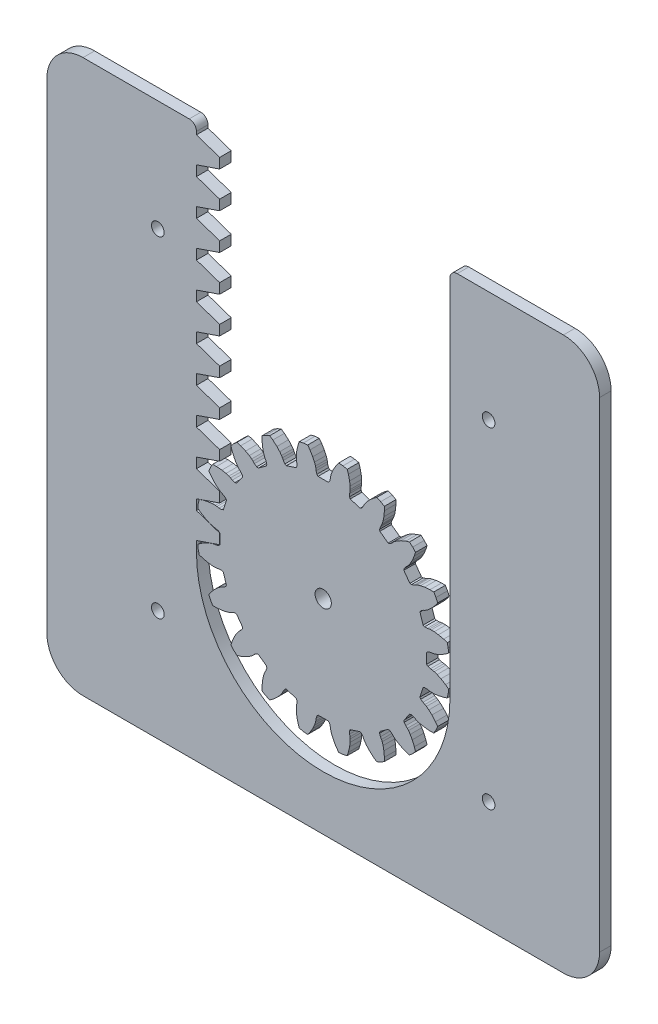
SolidWorks part; units mm, degrees
ref_plane "Front Plane" through (0, 0, 0) normal (0, 0, 1) x (1, 0, 0)
ref_plane "Top Plane" through (0, 0, 0) normal (0, 1, 0) x (1, 0, 0)
ref_plane "Right Plane" through (0, 0, 0) normal (1, 0, 0) x (0, 0, -1)
sketch "Model" plane through (0, 0, 0) normal (0, 0, 1) x (1, 0, 0)
  line L0 (-3.2331, -203.5925) -> (3.1831, -201.398)
  line L1 (3.1831, -201.398) -> (3.1831, -198.602)
  line L2 (3.1831, -198.602) -> (-3.2331, -196.4075)
  line L3 (-3.2331, -196.4075) -> (-3.2331, -193.5925)
  line L4 (-3.2331, -193.5925) -> (3.1831, -191.398)
  line L5 (3.1831, -191.398) -> (3.1831, -188.602)
  line L6 (3.1831, -188.602) -> (-3.2331, -186.4075)
  line L7 (-3.2331, -186.4075) -> (-3.2331, -183.5925)
  line L8 (-3.2331, -183.5925) -> (3.1831, -181.398)
  line L9 (3.1831, -181.398) -> (3.1831, -178.602)
  line L10 (3.1831, -178.602) -> (-3.2331, -176.4075)
  line L11 (-3.2331, -176.4075) -> (-3.2331, -173.5925)
  line L12 (-3.2331, -173.5925) -> (3.1831, -171.398)
  line L13 (3.1831, -171.398) -> (3.1831, -168.602)
  line L14 (3.1831, -168.602) -> (-3.2331, -166.4075)
  line L15 (-3.2331, -166.4075) -> (-3.2331, -163.5925)
  line L16 (-3.2331, -163.5925) -> (3.1831, -161.398)
  line L17 (3.1831, -161.398) -> (3.1831, -158.602)
  line L18 (3.1831, -158.602) -> (-3.2331, -156.4075)
  line L19 (-3.2331, -156.4075) -> (-3.2331, -153.5925)
  line L20 (-3.2331, -153.5925) -> (3.1831, -151.398)
  line L21 (3.1831, -151.398) -> (3.1831, -148.602)
  line L22 (3.1831, -148.602) -> (-3.2331, -146.4075)
  line L23 (-3.2331, -146.4075) -> (-3.2331, -143.5925)
  line L24 (-3.2331, -143.5925) -> (3.1831, -141.398)
  line L25 (3.1831, -141.398) -> (3.1831, -138.602)
  line L26 (3.1831, -138.602) -> (-3.2331, -136.4075)
  line L27 (-3.2331, -136.4075) -> (-3.2331, -133.5925)
  line L28 (-3.2331, -133.5925) -> (3.1831, -131.398)
  line L29 (3.1831, -131.398) -> (3.1831, -128.602)
  line L30 (3.1831, -128.602) -> (-3.2331, -126.4075)
  line L31 (-3.2331, -126.4075) -> (-3.2331, -123.5925)
  line L32 (-3.2331, -123.5925) -> (3.1831, -121.398)
  line L33 (3.1831, -121.398) -> (3.1831, -118.602)
  line L34 (3.1831, -118.602) -> (-3.2331, -116.4075)
  line L35 (-3.2331, -116.4075) -> (-3.2331, -113.5925)
  line L36 (-3.2331, -113.5925) -> (3.1831, -111.398)
  line L37 (3.1831, -111.398) -> (3.1831, -108.602)
  line L38 (3.1831, -108.602) -> (-3.2331, -106.4075)
  line L39 (-3.2331, -106.4075) -> (-3.2331, -103.5925)
  line L40 (-3.2331, -103.5925) -> (3.1831, -101.398)
  line L41 (3.1831, -101.398) -> (3.1831, -98.602)
  line L42 (3.1831, -98.602) -> (-3.2331, -96.4075)
  line L43 (-3.2331, -96.4075) -> (-3.2331, -93.5925)
  line L44 (-3.2331, -93.5925) -> (3.1831, -91.398)
  line L45 (3.1831, -91.398) -> (3.1831, -88.602)
  line L46 (3.1831, -88.602) -> (-3.2331, -86.4075)
  line L47 (-3.2331, -86.4075) -> (-3.2331, -83.5925)
  line L48 (-3.2331, -83.5925) -> (3.1831, -81.398)
  line L49 (3.1831, -81.398) -> (3.1831, -78.602)
  line L50 (3.1831, -78.602) -> (-3.2331, -76.4075)
  line L51 (-3.2331, -76.4075) -> (-3.2331, -73.5925)
  line L52 (-3.2331, -73.5925) -> (3.1831, -71.398)
  line L53 (3.1831, -71.398) -> (3.1831, -68.602)
  line L54 (3.1831, -68.602) -> (-3.2331, -66.4075)
  line L55 (-3.2331, -66.4075) -> (-3.2331, -63.5925)
  line L56 (-3.2331, -63.5925) -> (3.1831, -61.398)
  line L57 (3.1831, -61.398) -> (3.1831, -58.602)
  line L58 (3.1831, -58.602) -> (-3.2331, -56.4075)
  line L59 (-3.2331, -56.4075) -> (-3.2331, -53.5925)
  line L60 (-3.2331, -53.5925) -> (3.1831, -51.398)
  line L61 (3.1831, -51.398) -> (3.1831, -48.602)
  line L62 (3.1831, -48.602) -> (-3.2331, -46.4075)
  line L63 (-3.2331, -46.4075) -> (-3.2331, -43.5925)
  line L64 (-3.2331, -43.5925) -> (3.1831, -41.398)
  line L65 (3.1831, -41.398) -> (3.1831, -38.602)
  line L66 (3.1831, -38.602) -> (-3.2331, -36.4075)
  line L67 (-3.2331, -36.4075) -> (-3.2331, -33.5925)
  line L68 (-3.2331, -33.5925) -> (3.1831, -31.398)
  line L69 (3.1831, -31.398) -> (3.1831, -28.602)
  line L70 (3.1831, -28.602) -> (-3.2331, -26.4075)
  line L71 (-3.2331, -26.4075) -> (-3.2331, -23.5925)
  line L72 (-3.2331, -23.5925) -> (3.1831, -21.398)
  line L73 (3.1831, -21.398) -> (3.1831, -18.602)
  line L74 (3.1831, -18.602) -> (-3.2331, -16.4075)
  line L75 (-3.2331, -16.4075) -> (-3.2331, -13.5925)
  line L76 (-3.2331, -13.5925) -> (3.1831, -11.398)
  line L77 (3.1831, -11.398) -> (3.1831, -8.602)
  line L78 (3.1831, -8.602) -> (-3.2331, -6.4075)
  line L79 (-3.2331, -6.4075) -> (-3.2331, -3.5925)
  line L80 (-3.2331, -3.5925) -> (3.1831, -1.398)
  line L81 (3.1831, -1.398) -> (3.1831, 1.398)
  line L82 (3.1831, 1.398) -> (-3.2331, 3.5925)
  line L83 (-3.2331, 3.5925) -> (-3.2331, 6.4075)
  line L84 (-3.2331, 6.4075) -> (3.1831, 8.602)
  line L85 (3.1831, 8.602) -> (3.1831, 11.398)
  line L86 (3.1831, 11.398) -> (-3.2331, 13.5925)
  line L87 (-3.2331, 13.5925) -> (-3.2331, 16.4075)
  line L88 (-3.2331, 16.4075) -> (3.1831, 18.602)
  line L89 (3.1831, 18.602) -> (3.1831, 21.398)
  line L90 (3.1831, 21.398) -> (-3.2331, 23.5925)
  line L91 (-3.2331, 23.5925) -> (-3.2331, 26.4075)
  line L92 (-3.2331, 26.4075) -> (3.1831, 28.602)
  line L93 (3.1831, 28.602) -> (3.1831, 31.398)
  line L94 (3.1831, 31.398) -> (-3.2331, 33.5925)
  line L95 (-3.2331, 33.5925) -> (-3.2331, 36.4075)
  line L96 (-3.2331, 36.4075) -> (3.1831, 38.602)
  line L97 (3.1831, 38.602) -> (3.1831, 41.398)
  line L98 (3.1831, 41.398) -> (-3.2331, 43.5925)
  line L99 (-3.2331, 43.5925) -> (-3.2331, 46.4075)
  line L100 (-3.2331, 46.4075) -> (3.1831, 48.602)
  line L101 (3.1831, 48.602) -> (3.1831, 51.398)
  line L102 (3.1831, 51.398) -> (-3.2331, 53.5925)
  line L103 (-3.2331, 53.5925) -> (-3.2331, 56.4075)
  line L104 (-3.2331, 56.4075) -> (3.1831, 58.602)
  line L105 (3.1831, 58.602) -> (3.1831, 61.398)
  line L106 (3.1831, 61.398) -> (-3.2331, 63.5925)
  line L107 (-3.2331, 63.5925) -> (-3.2331, 66.4075)
  line L108 (-3.2331, 66.4075) -> (3.1831, 68.602)
  line L109 (3.1831, 68.602) -> (3.1831, 71.398)
  line L110 (3.1831, 71.398) -> (-3.2331, 73.5925)
  line L111 (-3.2331, 73.5925) -> (-3.2331, 76.4075)
  line L112 (-3.2331, 76.4075) -> (3.1831, 78.602)
  line L113 (3.1831, 78.602) -> (3.1831, 81.398)
  line L114 (3.1831, 81.398) -> (-3.2331, 83.5925)
  line L115 (-3.2331, 83.5925) -> (-3.2331, 86.4075)
  line L116 (-3.2331, 86.4075) -> (3.1831, 88.602)
  line L117 (3.1831, 88.602) -> (3.1831, 91.398)
  line L118 (3.1831, 91.398) -> (-3.2331, 93.5925)
  line L119 (-3.2331, 93.5925) -> (-3.2331, 96.4075)
  line L120 (-3.2331, 96.4075) -> (3.1831, 98.602)
  line L121 (3.1831, 98.602) -> (3.1831, 101.398)
  line L122 (3.1831, 101.398) -> (-3.2331, 103.5925)
  line L123 (-3.2331, 103.5925) -> (-3.2331, 106.4075)
  line L124 (-3.2331, 106.4075) -> (3.1831, 108.602)
  line L125 (3.1831, 108.602) -> (3.1831, 111.398)
  line L126 (3.1831, 111.398) -> (-3.2331, 113.5925)
  line L127 (-3.2331, 113.5925) -> (-3.2331, 116.4075)
  line L128 (-3.2331, 116.4075) -> (3.1831, 118.602)
  line L129 (3.1831, 118.602) -> (3.1831, 121.398)
  line L130 (3.1831, 121.398) -> (-3.2331, 123.5925)
  line L131 (-3.2331, 123.5925) -> (-3.2331, 126.4075)
  line L132 (-3.2331, 126.4075) -> (3.1831, 128.602)
  line L133 (3.1831, 128.602) -> (3.1831, 131.398)
  line L134 (3.1831, 131.398) -> (-3.2331, 133.5925)
  line L135 (-3.2331, 133.5925) -> (-3.2331, 136.4075)
  line L136 (-3.2331, 136.4075) -> (3.1831, 138.602)
  line L137 (3.1831, 138.602) -> (3.1831, 141.398)
  line L138 (3.1831, 141.398) -> (-3.2331, 143.5925)
  line L139 (-3.2331, 143.5925) -> (-3.2331, 146.4075)
  line L140 (-3.2331, 146.4075) -> (3.1831, 148.602)
  line L141 (3.1831, 148.602) -> (3.1831, 151.398)
  line L142 (3.1831, 151.398) -> (-3.2331, 153.5925)
  line L143 (-3.2331, 153.5925) -> (-3.2331, 156.4075)
  line L144 (-3.2331, 156.4075) -> (3.1831, 158.602)
  line L145 (3.1831, 158.602) -> (3.1831, 161.398)
  line L146 (3.1831, 161.398) -> (-3.2331, 163.5925)
  line L147 (-3.2331, 163.5925) -> (-3.2331, 166.4075)
  line L148 (-3.2331, 166.4075) -> (3.1831, 168.602)
  line L149 (3.1831, 168.602) -> (3.1831, 171.398)
  line L150 (3.1831, 171.398) -> (-3.2331, 173.5925)
  line L151 (-3.2331, 173.5925) -> (-3.2331, 176.4075)
  line L152 (-3.2331, 176.4075) -> (3.1831, 178.602)
  line L153 (3.1831, 178.602) -> (3.1831, 181.398)
  line L154 (3.1831, 181.398) -> (-3.2331, 183.5925)
  line L155 (-3.2331, 183.5925) -> (-3.2331, 186.4075)
  line L156 (-3.2331, 186.4075) -> (3.1831, 188.602)
  line L157 (3.1831, 188.602) -> (3.1831, 191.398)
  line L158 (3.1831, 191.398) -> (-3.2331, 193.5925)
  line L159 (-3.2331, 193.5925) -> (-3.2331, 196.4075)
  line L160 (-3.2331, 196.4075) -> (3.1831, 198.602)
  line L161 (3.1831, 198.602) -> (3.1831, 201.398)
  line L162 (3.1831, 201.398) -> (-3.2331, 203.5925)
  line L163 (-3.2331, 203.5925) -> (-3.2331, 205)
  line L164 (-3.2331, 205) -> (-15.9655, 205)
  line L165 (-15.9655, 205) -> (-15.9655, -205)
  line L166 (-15.9655, -205) -> (-3.2331, -205)
  line L167 (-3.2331, -205) -> (-3.2331, -203.5925)
  line L168 (-2.4761, 6.6265) -> (-2.752, 5.4774)
  line L169 (-2.752, 5.4774) -> (-2.8447, 4.2993)
  line L170 (-2.8447, 4.2993) -> (-2.0018, 3.6669)
  line L171 (-2.0018, 3.6669) -> (-0.7228, 2.9019)
  line L172 (-0.7228, 2.9019) -> (0.3292, 2.414)
  line L173 (0.3292, 2.414) -> (1.1138, 2.1457)
  line L174 (1.1138, 2.1457) -> (1.5998, 2.0345)
  line L175 (1.5998, 2.0345) -> (2.1765, 1.9649)
  line L176 (2.1765, 1.9649) -> (2.8928, 1.7388)
  line L177 (2.8928, 1.7388) -> (3.2331, 1.4208)
  line L178 (3.2331, 1.4208) -> (3.2331, -1.4208)
  line L179 (3.2331, -1.4208) -> (2.8928, -1.7388)
  line L180 (2.8928, -1.7388) -> (2.1765, -1.9649)
  line L181 (2.1765, -1.9649) -> (1.5998, -2.0345)
  line L182 (1.5998, -2.0345) -> (1.1138, -2.1457)
  line L183 (1.1138, -2.1457) -> (0.3292, -2.414)
  line L184 (0.3292, -2.414) -> (-0.7228, -2.9019)
  line L185 (-0.7228, -2.9019) -> (-2.0018, -3.6669)
  line L186 (-2.0018, -3.6669) -> (-2.8447, -4.2993)
  line L187 (-2.8447, -4.2993) -> (-2.752, -5.4774)
  line L188 (-2.752, -5.4774) -> (-2.4761, -6.6265)
  line L189 (-2.4761, -6.6265) -> (-1.4791, -6.9675)
  line L190 (-1.4791, -6.9675) -> (-0.0263, -7.2998)
  line L191 (-0.0263, -7.2998) -> (1.1251, -7.4387)
  line L192 (1.1251, -7.4387) -> (1.9541, -7.4515)
  line L193 (1.9541, -7.4515) -> (2.4507, -7.407)
  line L194 (2.4507, -7.407) -> (3.0207, -7.295)
  line L195 (3.0207, -7.295) -> (3.7718, -7.2887)
  line L196 (3.7718, -7.2887) -> (4.1937, -7.486)
  line L197 (4.1937, -7.486) -> (5.0718, -10.1885)
  line L198 (5.0718, -10.1885) -> (4.8465, -10.5961)
  line L199 (4.8465, -10.5961) -> (4.2351, -11.0325)
  line L200 (4.2351, -11.0325) -> (3.7081, -11.2769)
  line L201 (3.7081, -11.2769) -> (3.2802, -11.5328)
  line L202 (3.2802, -11.5328) -> (2.617, -12.0304)
  line L203 (2.617, -12.0304) -> (1.7672, -12.8196)
  line L204 (1.7672, -12.8196) -> (0.7872, -13.9423)
  line L205 (0.7872, -13.9423) -> (0.181, -14.8043)
  line L206 (0.181, -14.8043) -> (0.6332, -15.8961)
  line L207 (0.6332, -15.8961) -> (1.2507, -16.9037)
  line L208 (1.2507, -16.9037) -> (2.3043, -16.9199)
  line L209 (2.3043, -16.9199) -> (3.7887, -16.7869)
  line L210 (3.7887, -16.7869) -> (4.9266, -16.5633)
  line L211 (4.9266, -16.5633) -> (5.719, -16.3192)
  line L212 (5.719, -16.3192) -> (6.1775, -16.1235)
  line L213 (6.1775, -16.1235) -> (6.6851, -15.8408)
  line L214 (6.6851, -15.8408) -> (7.3975, -15.6027)
  line L215 (7.3975, -15.6027) -> (7.8597, -15.66)
  line L216 (7.8597, -15.66) -> (9.5299, -17.9589)
  line L217 (9.5299, -17.9589) -> (9.4416, -18.4162)
  line L218 (9.4416, -18.4162) -> (8.995, -19.0201)
  line L219 (8.995, -19.0201) -> (8.5693, -19.4154)
  line L220 (8.5693, -19.4154) -> (8.2414, -19.791)
  line L221 (8.2414, -19.791) -> (7.7645, -20.4692)
  line L222 (7.7645, -20.4692) -> (7.2001, -21.4824)
  line L223 (7.2001, -21.4824) -> (6.615, -22.853)
  line L224 (6.615, -22.853) -> (6.3048, -23.8601)
  line L225 (6.3048, -23.8601) -> (7.0723, -24.7587)
  line L226 (7.0723, -24.7587) -> (7.9709, -25.5262)
  line L227 (7.9709, -25.5262) -> (8.978, -25.216)
  line L228 (8.978, -25.216) -> (10.3486, -24.6309)
  line L229 (10.3486, -24.6309) -> (11.3618, -24.0665)
  line L230 (11.3618, -24.0665) -> (12.04, -23.5896)
  line L231 (12.04, -23.5896) -> (12.4155, -23.2617)
  line L232 (12.4155, -23.2617) -> (12.8109, -22.836)
  line L233 (12.8109, -22.836) -> (13.4148, -22.3894)
  line L234 (13.4148, -22.3894) -> (13.8721, -22.301)
  line L235 (13.8721, -22.301) -> (16.171, -23.9713)
  line L236 (16.171, -23.9713) -> (16.2283, -24.4335)
  line L237 (16.2283, -24.4335) -> (15.9902, -25.1459)
  line L238 (15.9902, -25.1459) -> (15.7075, -25.6535)
  line L239 (15.7075, -25.6535) -> (15.5117, -26.112)
  line L240 (15.5117, -26.112) -> (15.2677, -26.9044)
  line L241 (15.2677, -26.9044) -> (15.0441, -28.0423)
  line L242 (15.0441, -28.0423) -> (14.9111, -29.5267)
  line L243 (14.9111, -29.5267) -> (14.9273, -30.5803)
  line L244 (14.9273, -30.5803) -> (15.9349, -31.1978)
  line L245 (15.9349, -31.1978) -> (17.0267, -31.65)
  line L246 (17.0267, -31.65) -> (17.8887, -31.0438)
  line L247 (17.8887, -31.0438) -> (19.0114, -30.0638)
  line L248 (19.0114, -30.0638) -> (19.8006, -29.214)
  line L249 (19.8006, -29.214) -> (20.2982, -28.5508)
  line L250 (20.2982, -28.5508) -> (20.5541, -28.1229)
  line L251 (20.5541, -28.1229) -> (20.7985, -27.5959)
  line L252 (20.7985, -27.5959) -> (21.2349, -26.9845)
  line L253 (21.2349, -26.9845) -> (21.6425, -26.7592)
  line L254 (21.6425, -26.7592) -> (24.345, -27.6373)
  line L255 (24.345, -27.6373) -> (24.5423, -28.0592)
  line L256 (24.5423, -28.0592) -> (24.536, -28.8102)
  line L257 (24.536, -28.8102) -> (24.424, -29.3803)
  line L258 (24.424, -29.3803) -> (24.3795, -29.8769)
  line L259 (24.3795, -29.8769) -> (24.3923, -30.7059)
  line L260 (24.3923, -30.7059) -> (24.5312, -31.8573)
  line L261 (24.5312, -31.8573) -> (24.8635, -33.3101)
  line L262 (24.8635, -33.3101) -> (25.2045, -34.3071)
  line L263 (25.2045, -34.3071) -> (26.3536, -34.583)
  line L264 (26.3536, -34.583) -> (27.5317, -34.6757)
  line L265 (27.5317, -34.6757) -> (28.1641, -33.8328)
  line L266 (28.1641, -33.8328) -> (28.929, -32.5538)
  line L267 (28.929, -32.5538) -> (29.417, -31.5017)
  line L268 (29.417, -31.5017) -> (29.6853, -30.7172)
  line L269 (29.6853, -30.7172) -> (29.7965, -30.2312)
  line L270 (29.7965, -30.2312) -> (29.8661, -29.6544)
  line L271 (29.8661, -29.6544) -> (30.0922, -28.9382)
  line L272 (30.0922, -28.9382) -> (30.4102, -28.5979)
  line L273 (30.4102, -28.5979) -> (33.2518, -28.5979)
  line L274 (33.2518, -28.5979) -> (33.5698, -28.9382)
  line L275 (33.5698, -28.9382) -> (33.7959, -29.6544)
  line L276 (33.7959, -29.6544) -> (33.8655, -30.2312)
  line L277 (33.8655, -30.2312) -> (33.9767, -30.7172)
  line L278 (33.9767, -30.7172) -> (34.245, -31.5017)
  line L279 (34.245, -31.5017) -> (34.7329, -32.5538)
  line L280 (34.7329, -32.5538) -> (35.4979, -33.8328)
  line L281 (35.4979, -33.8328) -> (36.1303, -34.6757)
  line L282 (36.1303, -34.6757) -> (37.3084, -34.583)
  line L283 (37.3084, -34.583) -> (38.4575, -34.3071)
  line L284 (38.4575, -34.3071) -> (38.7985, -33.3101)
  line L285 (38.7985, -33.3101) -> (39.1308, -31.8573)
  line L286 (39.1308, -31.8573) -> (39.2697, -30.7059)
  line L287 (39.2697, -30.7059) -> (39.2825, -29.8769)
  line L288 (39.2825, -29.8769) -> (39.238, -29.3803)
  line L289 (39.238, -29.3803) -> (39.126, -28.8102)
  line L290 (39.126, -28.8102) -> (39.1197, -28.0592)
  line L291 (39.1197, -28.0592) -> (39.3169, -27.6373)
  line L292 (39.3169, -27.6373) -> (42.0195, -26.7592)
  line L293 (42.0195, -26.7592) -> (42.4271, -26.9845)
  line L294 (42.4271, -26.9845) -> (42.8635, -27.5959)
  line L295 (42.8635, -27.5959) -> (43.1079, -28.1229)
  line L296 (43.1079, -28.1229) -> (43.3638, -28.5508)
  line L297 (43.3638, -28.5508) -> (43.8614, -29.214)
  line L298 (43.8614, -29.214) -> (44.6506, -30.0638)
  line L299 (44.6506, -30.0638) -> (45.7733, -31.0438)
  line L300 (45.7733, -31.0438) -> (46.6353, -31.65)
  line L301 (46.6353, -31.65) -> (47.7271, -31.1978)
  line L302 (47.7271, -31.1978) -> (48.7347, -30.5803)
  line L303 (48.7347, -30.5803) -> (48.7509, -29.5267)
  line L304 (48.7509, -29.5267) -> (48.6179, -28.0423)
  line L305 (48.6179, -28.0423) -> (48.3943, -26.9044)
  line L306 (48.3943, -26.9044) -> (48.1502, -26.112)
  line L307 (48.1502, -26.112) -> (47.9545, -25.6535)
  line L308 (47.9545, -25.6535) -> (47.6718, -25.1459)
  line L309 (47.6718, -25.1459) -> (47.4337, -24.4335)
  line L310 (47.4337, -24.4335) -> (47.4909, -23.9713)
  line L311 (47.4909, -23.9713) -> (49.7899, -22.301)
  line L312 (49.7899, -22.301) -> (50.2472, -22.3894)
  line L313 (50.2472, -22.3894) -> (50.8511, -22.836)
  line L314 (50.8511, -22.836) -> (51.2464, -23.2617)
  line L315 (51.2464, -23.2617) -> (51.622, -23.5896)
  line L316 (51.622, -23.5896) -> (52.3002, -24.0665)
  line L317 (52.3002, -24.0665) -> (53.3134, -24.6309)
  line L318 (53.3134, -24.6309) -> (54.684, -25.216)
  line L319 (54.684, -25.216) -> (55.6911, -25.5262)
  line L320 (55.6911, -25.5262) -> (56.5897, -24.7587)
  line L321 (56.5897, -24.7587) -> (57.3572, -23.8601)
  line L322 (57.3572, -23.8601) -> (57.047, -22.853)
  line L323 (57.047, -22.853) -> (56.4619, -21.4824)
  line L324 (56.4619, -21.4824) -> (55.8975, -20.4692)
  line L325 (55.8975, -20.4692) -> (55.4206, -19.791)
  line L326 (55.4206, -19.791) -> (55.0927, -19.4154)
  line L327 (55.0927, -19.4154) -> (54.667, -19.0201)
  line L328 (54.667, -19.0201) -> (54.2204, -18.4162)
  line L329 (54.2204, -18.4162) -> (54.132, -17.9589)
  line L330 (54.132, -17.9589) -> (55.8023, -15.66)
  line L331 (55.8023, -15.66) -> (56.2645, -15.6027)
  line L332 (56.2645, -15.6027) -> (56.9769, -15.8408)
  line L333 (56.9769, -15.8408) -> (57.4844, -16.1235)
  line L334 (57.4844, -16.1235) -> (57.943, -16.3192)
  line L335 (57.943, -16.3192) -> (58.7353, -16.5633)
  line L336 (58.7353, -16.5633) -> (59.8733, -16.7869)
  line L337 (59.8733, -16.7869) -> (61.3577, -16.9199)
  line L338 (61.3577, -16.9199) -> (62.4113, -16.9037)
  line L339 (62.4113, -16.9037) -> (63.0288, -15.8961)
  line L340 (63.0288, -15.8961) -> (63.481, -14.8043)
  line L341 (63.481, -14.8043) -> (62.8748, -13.9423)
  line L342 (62.8748, -13.9423) -> (61.8948, -12.8196)
  line L343 (61.8948, -12.8196) -> (61.045, -12.0304)
  line L344 (61.045, -12.0304) -> (60.3818, -11.5328)
  line L345 (60.3818, -11.5328) -> (59.9539, -11.2769)
  line L346 (59.9539, -11.2769) -> (59.4268, -11.0325)
  line L347 (59.4268, -11.0325) -> (58.8155, -10.5961)
  line L348 (58.8155, -10.5961) -> (58.5901, -10.1885)
  line L349 (58.5901, -10.1885) -> (59.4683, -7.486)
  line L350 (59.4683, -7.486) -> (59.8901, -7.2887)
  line L351 (59.8901, -7.2887) -> (60.6412, -7.295)
  line L352 (60.6412, -7.295) -> (61.2113, -7.407)
  line L353 (61.2113, -7.407) -> (61.7079, -7.4515)
  line L354 (61.7079, -7.4515) -> (62.5369, -7.4387)
  line L355 (62.5369, -7.4387) -> (63.6883, -7.2998)
  line L356 (63.6883, -7.2998) -> (65.141, -6.9675)
  line L357 (65.141, -6.9675) -> (66.1381, -6.6265)
  line L358 (66.1381, -6.6265) -> (66.414, -5.4774)
  line L359 (66.414, -5.4774) -> (66.5067, -4.2993)
  line L360 (66.5067, -4.2993) -> (65.6638, -3.6669)
  line L361 (65.6638, -3.6669) -> (64.3848, -2.9019)
  line L362 (64.3848, -2.9019) -> (63.3327, -2.414)
  line L363 (63.3327, -2.414) -> (62.5482, -2.1457)
  line L364 (62.5482, -2.1457) -> (62.0622, -2.0345)
  line L365 (62.0622, -2.0345) -> (61.4854, -1.9649)
  line L366 (61.4854, -1.9649) -> (60.7692, -1.7388)
  line L367 (60.7692, -1.7388) -> (60.4289, -1.4208)
  line L368 (60.4289, -1.4208) -> (60.4289, 1.4208)
  line L369 (60.4289, 1.4208) -> (60.7692, 1.7388)
  line L370 (60.7692, 1.7388) -> (61.4854, 1.9649)
  line L371 (61.4854, 1.9649) -> (62.0622, 2.0345)
  line L372 (62.0622, 2.0345) -> (62.5482, 2.1457)
  line L373 (62.5482, 2.1457) -> (63.3327, 2.414)
  line L374 (63.3327, 2.414) -> (64.3848, 2.9019)
  line L375 (64.3848, 2.9019) -> (65.6638, 3.6669)
  line L376 (65.6638, 3.6669) -> (66.5067, 4.2993)
  line L377 (66.5067, 4.2993) -> (66.414, 5.4774)
  line L378 (66.414, 5.4774) -> (66.1381, 6.6265)
  line L379 (66.1381, 6.6265) -> (65.141, 6.9675)
  line L380 (65.141, 6.9675) -> (63.6883, 7.2998)
  line L381 (63.6883, 7.2998) -> (62.5369, 7.4387)
  line L382 (62.5369, 7.4387) -> (61.7079, 7.4515)
  line L383 (61.7079, 7.4515) -> (61.2113, 7.407)
  line L384 (61.2113, 7.407) -> (60.6412, 7.295)
  line L385 (60.6412, 7.295) -> (59.8901, 7.2887)
  line L386 (59.8901, 7.2887) -> (59.4683, 7.486)
  line L387 (59.4683, 7.486) -> (58.5901, 10.1885)
  line L388 (58.5901, 10.1885) -> (58.8155, 10.5961)
  line L389 (58.8155, 10.5961) -> (59.4268, 11.0325)
  line L390 (59.4268, 11.0325) -> (59.9539, 11.2769)
  line L391 (59.9539, 11.2769) -> (60.3818, 11.5328)
  line L392 (60.3818, 11.5328) -> (61.045, 12.0304)
  line L393 (61.045, 12.0304) -> (61.8948, 12.8196)
  line L394 (61.8948, 12.8196) -> (62.8748, 13.9423)
  line L395 (62.8748, 13.9423) -> (63.481, 14.8043)
  line L396 (63.481, 14.8043) -> (63.0288, 15.8961)
  line L397 (63.0288, 15.8961) -> (62.4113, 16.9037)
  line L398 (62.4113, 16.9037) -> (61.3577, 16.9199)
  line L399 (61.3577, 16.9199) -> (59.8733, 16.7869)
  line L400 (59.8733, 16.7869) -> (58.7353, 16.5633)
  line L401 (58.7353, 16.5633) -> (57.943, 16.3192)
  line L402 (57.943, 16.3192) -> (57.4844, 16.1235)
  line L403 (57.4844, 16.1235) -> (56.9769, 15.8408)
  line L404 (56.9769, 15.8408) -> (56.2645, 15.6027)
  line L405 (56.2645, 15.6027) -> (55.8023, 15.66)
  line L406 (55.8023, 15.66) -> (54.132, 17.9589)
  line L407 (54.132, 17.9589) -> (54.2204, 18.4162)
  line L408 (54.2204, 18.4162) -> (54.667, 19.0201)
  line L409 (54.667, 19.0201) -> (55.0927, 19.4154)
  line L410 (55.0927, 19.4154) -> (55.4206, 19.791)
  line L411 (55.4206, 19.791) -> (55.8975, 20.4692)
  line L412 (55.8975, 20.4692) -> (56.4619, 21.4824)
  line L413 (56.4619, 21.4824) -> (57.047, 22.853)
  line L414 (57.047, 22.853) -> (57.3572, 23.8601)
  line L415 (57.3572, 23.8601) -> (56.5897, 24.7587)
  line L416 (56.5897, 24.7587) -> (55.6911, 25.5262)
  line L417 (55.6911, 25.5262) -> (54.684, 25.216)
  line L418 (54.684, 25.216) -> (53.3134, 24.6309)
  line L419 (53.3134, 24.6309) -> (52.3002, 24.0665)
  line L420 (52.3002, 24.0665) -> (51.622, 23.5896)
  line L421 (51.622, 23.5896) -> (51.2464, 23.2617)
  line L422 (51.2464, 23.2617) -> (50.8511, 22.836)
  line L423 (50.8511, 22.836) -> (50.2472, 22.3894)
  line L424 (50.2472, 22.3894) -> (49.7899, 22.301)
  line L425 (49.7899, 22.301) -> (47.4909, 23.9713)
  line L426 (47.4909, 23.9713) -> (47.4337, 24.4335)
  line L427 (47.4337, 24.4335) -> (47.6718, 25.1459)
  line L428 (47.6718, 25.1459) -> (47.9545, 25.6535)
  line L429 (47.9545, 25.6535) -> (48.1502, 26.112)
  line L430 (48.1502, 26.112) -> (48.3943, 26.9044)
  line L431 (48.3943, 26.9044) -> (48.6179, 28.0423)
  line L432 (48.6179, 28.0423) -> (48.7509, 29.5267)
  line L433 (48.7509, 29.5267) -> (48.7347, 30.5803)
  line L434 (48.7347, 30.5803) -> (47.7271, 31.1978)
  line L435 (47.7271, 31.1978) -> (46.6353, 31.65)
  line L436 (46.6353, 31.65) -> (45.7733, 31.0438)
  line L437 (45.7733, 31.0438) -> (44.6506, 30.0638)
  line L438 (44.6506, 30.0638) -> (43.8614, 29.214)
  line L439 (43.8614, 29.214) -> (43.3638, 28.5508)
  line L440 (43.3638, 28.5508) -> (43.1079, 28.1229)
  line L441 (43.1079, 28.1229) -> (42.8635, 27.5959)
  line L442 (42.8635, 27.5959) -> (42.4271, 26.9845)
  line L443 (42.4271, 26.9845) -> (42.0195, 26.7592)
  line L444 (42.0195, 26.7592) -> (39.3169, 27.6373)
  line L445 (39.3169, 27.6373) -> (39.1197, 28.0592)
  line L446 (39.1197, 28.0592) -> (39.126, 28.8102)
  line L447 (39.126, 28.8102) -> (39.238, 29.3803)
  line L448 (39.238, 29.3803) -> (39.2825, 29.8769)
  line L449 (39.2825, 29.8769) -> (39.2697, 30.7059)
  line L450 (39.2697, 30.7059) -> (39.1308, 31.8573)
  line L451 (39.1308, 31.8573) -> (38.7985, 33.3101)
  line L452 (38.7985, 33.3101) -> (38.4575, 34.3071)
  line L453 (38.4575, 34.3071) -> (37.3084, 34.583)
  line L454 (37.3084, 34.583) -> (36.1303, 34.6757)
  line L455 (36.1303, 34.6757) -> (35.4979, 33.8328)
  line L456 (35.4979, 33.8328) -> (34.7329, 32.5538)
  line L457 (34.7329, 32.5538) -> (34.245, 31.5017)
  line L458 (34.245, 31.5017) -> (33.9767, 30.7172)
  line L459 (33.9767, 30.7172) -> (33.8655, 30.2312)
  line L460 (33.8655, 30.2312) -> (33.7959, 29.6544)
  line L461 (33.7959, 29.6544) -> (33.5698, 28.9382)
  line L462 (33.5698, 28.9382) -> (33.2518, 28.5979)
  line L463 (33.2518, 28.5979) -> (30.4102, 28.5979)
  line L464 (30.4102, 28.5979) -> (30.0922, 28.9382)
  line L465 (30.0922, 28.9382) -> (29.8661, 29.6544)
  line L466 (29.8661, 29.6544) -> (29.7965, 30.2312)
  line L467 (29.7965, 30.2312) -> (29.6853, 30.7172)
  line L468 (29.6853, 30.7172) -> (29.417, 31.5017)
  line L469 (29.417, 31.5017) -> (28.929, 32.5538)
  line L470 (28.929, 32.5538) -> (28.1641, 33.8328)
  line L471 (28.1641, 33.8328) -> (27.5317, 34.6757)
  line L472 (27.5317, 34.6757) -> (26.3536, 34.583)
  line L473 (26.3536, 34.583) -> (25.2045, 34.3071)
  line L474 (25.2045, 34.3071) -> (24.8635, 33.3101)
  line L475 (24.8635, 33.3101) -> (24.5312, 31.8573)
  line L476 (24.5312, 31.8573) -> (24.3923, 30.7059)
  line L477 (24.3923, 30.7059) -> (24.3795, 29.8769)
  line L478 (24.3795, 29.8769) -> (24.424, 29.3803)
  line L479 (24.424, 29.3803) -> (24.536, 28.8102)
  line L480 (24.536, 28.8102) -> (24.5423, 28.0592)
  line L481 (24.5423, 28.0592) -> (24.345, 27.6373)
  line L482 (24.345, 27.6373) -> (21.6425, 26.7592)
  line L483 (21.6425, 26.7592) -> (21.2349, 26.9845)
  line L484 (21.2349, 26.9845) -> (20.7985, 27.5959)
  line L485 (20.7985, 27.5959) -> (20.5541, 28.1229)
  line L486 (20.5541, 28.1229) -> (20.2982, 28.5508)
  line L487 (20.2982, 28.5508) -> (19.8006, 29.214)
  line L488 (19.8006, 29.214) -> (19.0114, 30.0638)
  line L489 (19.0114, 30.0638) -> (17.8887, 31.0438)
  line L490 (17.8887, 31.0438) -> (17.0267, 31.65)
  line L491 (17.0267, 31.65) -> (15.9349, 31.1978)
  line L492 (15.9349, 31.1978) -> (14.9273, 30.5803)
  line L493 (14.9273, 30.5803) -> (14.9111, 29.5267)
  line L494 (14.9111, 29.5267) -> (15.0441, 28.0423)
  line L495 (15.0441, 28.0423) -> (15.2677, 26.9044)
  line L496 (15.2677, 26.9044) -> (15.5117, 26.112)
  line L497 (15.5117, 26.112) -> (15.7075, 25.6535)
  line L498 (15.7075, 25.6535) -> (15.9902, 25.1459)
  line L499 (15.9902, 25.1459) -> (16.2283, 24.4335)
  line L500 (16.2283, 24.4335) -> (16.171, 23.9713)
  line L501 (16.171, 23.9713) -> (13.8721, 22.301)
  line L502 (13.8721, 22.301) -> (13.4148, 22.3894)
  line L503 (13.4148, 22.3894) -> (12.8109, 22.836)
  line L504 (12.8109, 22.836) -> (12.4155, 23.2617)
  line L505 (12.4155, 23.2617) -> (12.04, 23.5896)
  line L506 (12.04, 23.5896) -> (11.3618, 24.0665)
  line L507 (11.3618, 24.0665) -> (10.3486, 24.6309)
  line L508 (10.3486, 24.6309) -> (8.978, 25.216)
  line L509 (8.978, 25.216) -> (7.9709, 25.5262)
  line L510 (7.9709, 25.5262) -> (7.0723, 24.7587)
  line L511 (7.0723, 24.7587) -> (6.3048, 23.8601)
  line L512 (6.3048, 23.8601) -> (6.615, 22.853)
  line L513 (6.615, 22.853) -> (7.2001, 21.4824)
  line L514 (7.2001, 21.4824) -> (7.7645, 20.4692)
  line L515 (7.7645, 20.4692) -> (8.2414, 19.791)
  line L516 (8.2414, 19.791) -> (8.5693, 19.4154)
  line L517 (8.5693, 19.4154) -> (8.995, 19.0201)
  line L518 (8.995, 19.0201) -> (9.4416, 18.4162)
  line L519 (9.4416, 18.4162) -> (9.5299, 17.9589)
  line L520 (9.5299, 17.9589) -> (7.8597, 15.66)
  line L521 (7.8597, 15.66) -> (7.3975, 15.6027)
  line L522 (7.3975, 15.6027) -> (6.6851, 15.8408)
  line L523 (6.6851, 15.8408) -> (6.1775, 16.1235)
  line L524 (6.1775, 16.1235) -> (5.719, 16.3192)
  line L525 (5.719, 16.3192) -> (4.9266, 16.5633)
  line L526 (4.9266, 16.5633) -> (3.7887, 16.7869)
  line L527 (3.7887, 16.7869) -> (2.3043, 16.9199)
  line L528 (2.3043, 16.9199) -> (1.2507, 16.9037)
  line L529 (1.2507, 16.9037) -> (0.6332, 15.8961)
  line L530 (0.6332, 15.8961) -> (0.181, 14.8043)
  line L531 (0.181, 14.8043) -> (0.7872, 13.9423)
  line L532 (0.7872, 13.9423) -> (1.7672, 12.8196)
  line L533 (1.7672, 12.8196) -> (2.617, 12.0304)
  line L534 (2.617, 12.0304) -> (3.2802, 11.5328)
  line L535 (3.2802, 11.5328) -> (3.7081, 11.2769)
  line L536 (3.7081, 11.2769) -> (4.2351, 11.0325)
  line L537 (4.2351, 11.0325) -> (4.8465, 10.5961)
  line L538 (4.8465, 10.5961) -> (5.0718, 10.1885)
  line L539 (5.0718, 10.1885) -> (4.1937, 7.486)
  line L540 (4.1937, 7.486) -> (3.7718, 7.2887)
  line L541 (3.7718, 7.2887) -> (3.0207, 7.295)
  line L542 (3.0207, 7.295) -> (2.4507, 7.407)
  line L543 (2.4507, 7.407) -> (1.9541, 7.4515)
  line L544 (1.9541, 7.4515) -> (1.1251, 7.4387)
  line L545 (1.1251, 7.4387) -> (-0.0263, 7.2998)
  line L546 (-0.0263, 7.2998) -> (-1.4791, 6.9675)
  line L547 (-1.4791, 6.9675) -> (-2.4761, 6.6265)
  line L548 (31.0247, 2.1006) -> (31.479, 2.2223)
  line L549 (31.479, 2.2223) -> (31.9487, 2.2469)
  line L550 (31.9487, 2.2469) -> (32.4133, 2.1733)
  line L551 (32.4133, 2.1733) -> (32.8525, 2.0048)
  line L552 (32.8525, 2.0048) -> (33.247, 1.7486)
  line L553 (33.247, 1.7486) -> (33.5796, 1.416)
  line L554 (33.5796, 1.416) -> (33.8358, 1.0215)
  line L555 (33.8358, 1.0215) -> (34.0043, 0.5823)
  line L556 (34.0043, 0.5823) -> (34.0779, 0.1178)
  line L557 (34.0779, 0.1178) -> (34.0533, -0.352)
  line L558 (34.0533, -0.352) -> (33.9315, -0.8063)
  line L559 (33.9315, -0.8063) -> (33.718, -1.2254)
  line L560 (33.718, -1.2254) -> (33.422, -1.591)
  line L561 (33.422, -1.591) -> (33.0564, -1.887)
  line L562 (33.0564, -1.887) -> (32.6373, -2.1006)
  line L563 (32.6373, -2.1006) -> (32.183, -2.2223)
  line L564 (32.183, -2.2223) -> (31.7132, -2.2469)
  line L565 (31.7132, -2.2469) -> (31.2486, -2.1733)
  line L566 (31.2486, -2.1733) -> (30.8095, -2.0048)
  line L567 (30.8095, -2.0048) -> (30.415, -1.7486)
  line L568 (30.415, -1.7486) -> (30.0824, -1.416)
  line L569 (30.0824, -1.416) -> (29.8262, -1.0215)
  line L570 (29.8262, -1.0215) -> (29.6577, -0.5823)
  line L571 (29.6577, -0.5823) -> (29.5841, -0.1178)
  line L572 (29.5841, -0.1178) -> (29.6087, 0.352)
  line L573 (29.6087, 0.352) -> (29.7304, 0.8063)
  line L574 (29.7304, 0.8063) -> (29.944, 1.2254)
  line L575 (29.944, 1.2254) -> (30.24, 1.591)
  line L576 (30.24, 1.591) -> (30.6056, 1.887)
  line L577 (30.6056, 1.887) -> (31.0247, 2.1006)
sketch "gear_body" plane through (0, 0, 0) normal (0, 0, 1) x (1, 0, 0)
  line L0 (0, 0) -> (31.831, 0) construction
  circle A0 centre (31.831, 0) radius 2.25
  circle A1 centre (31.831, 0) radius 31.831 construction
  circle A2 centre (31.831, 0) radius 35
  dimension "D1" = 31.831
  dimension "D2" = 70
  dimension "D3" = 4.5
sketch "rack" plane through (0, 0, 0) normal (0, 0, 1) x (1, 0, 0)
  line L0 (0, 0) -> (3.1831, 0) construction
  line L1 (0, 0) -> (31.831, 0) construction
  line L2 (-3.2331, -6.4075) -> (-3.2331, 96.4075) construction
  line L3 (-3.2331, -3.5925) -> (-3.2331, -6.4075)
  line L4 (0, -6.4075) -> (0, 96.4075) construction
  line L5 (3.1831, -6.4075) -> (3.1831, 96.4075) construction
  line L6 (-3.2331, -6.4075) -> (3.1831, -6.4075) construction
  line L7 (-3.2331, -3.5925) -> (3.1831, -1.398)
  line L8 (3.1831, -1.398) -> (3.1831, 1.398)
  line L9 (3.1831, 1.398) -> (-3.2331, 3.5925)
  line L10 (-3.2331, 3.5925) -> (-3.2331, 6.4075)
  line L11 (-3.2331, 96.4075) -> (3.1831, 96.4075) construction
  line L12 (-3.2331, 13.5925) -> (-3.2331, 16.4075)
  line L13 (3.1831, 11.398) -> (-3.2331, 13.5925)
  line L14 (3.1831, 8.602) -> (3.1831, 11.398)
  line L15 (-3.2331, 6.4075) -> (3.1831, 8.602)
  line L16 (-3.2331, 23.5925) -> (-3.2331, 26.4075)
  line L17 (3.1831, 21.398) -> (-3.2331, 23.5925)
  line L18 (3.1831, 18.602) -> (3.1831, 21.398)
  line L19 (-3.2331, 16.4075) -> (3.1831, 18.602)
  line L20 (-3.2331, 33.5925) -> (-3.2331, 36.4075)
  line L21 (3.1831, 31.398) -> (-3.2331, 33.5925)
  line L22 (3.1831, 28.602) -> (3.1831, 31.398)
  line L23 (-3.2331, 26.4075) -> (3.1831, 28.602)
  line L24 (-3.2331, 43.5925) -> (-3.2331, 46.4075)
  line L25 (3.1831, 41.398) -> (-3.2331, 43.5925)
  line L26 (3.1831, 38.602) -> (3.1831, 41.398)
  line L27 (-3.2331, 36.4075) -> (3.1831, 38.602)
  line L28 (-3.2331, 53.5925) -> (-3.2331, 56.4075)
  line L29 (3.1831, 51.398) -> (-3.2331, 53.5925)
  line L30 (3.1831, 48.602) -> (3.1831, 51.398)
  line L31 (-3.2331, 46.4075) -> (3.1831, 48.602)
  line L32 (-3.2331, 63.5925) -> (-3.2331, 66.4075)
  line L33 (3.1831, 61.398) -> (-3.2331, 63.5925)
  line L34 (3.1831, 58.602) -> (3.1831, 61.398)
  line L35 (-3.2331, 56.4075) -> (3.1831, 58.602)
  line L36 (-3.2331, 73.5925) -> (-3.2331, 76.4075)
  line L37 (3.1831, 71.398) -> (-3.2331, 73.5925)
  line L38 (3.1831, 68.602) -> (3.1831, 71.398)
  line L39 (-3.2331, 66.4075) -> (3.1831, 68.602)
  line L40 (-3.2331, 83.5925) -> (-3.2331, 86.4075)
  line L41 (3.1831, 81.398) -> (-3.2331, 83.5925)
  line L42 (3.1831, 78.602) -> (3.1831, 81.398)
  line L43 (-3.2331, 76.4075) -> (3.1831, 78.602)
  line L44 (-3.2331, 93.5925) -> (-3.2331, 96.4075)
  line L45 (3.1831, 91.398) -> (-3.2331, 93.5925)
  line L46 (3.1831, 88.602) -> (3.1831, 91.398)
  line L47 (-3.2331, 86.4075) -> (3.1831, 88.602)
  line L48 (3.1831, -6.4075) -> (31.831, -6.4075) construction
  line L49 (31.831, -6.4075) -> (31.831, 96.4075) construction
  line L50 (31.831, 96.4075) -> (3.1831, 96.4075) construction
  line L51 (31.831, -6.4075) -> (66.8951, -6.4075) construction
  line L52 (31.831, 45) -> (-3.2331, 45) construction
  line L53 (66.8951, -6.4075) -> (66.8951, 96.4075)
  line L54 (31.831, -6.4075) -> (31.831, -41.4716) construction
  line L55 (31.831, 96.4075) -> (31.831, 131.4716) construction
  arc A0 (-3.2331, -6.4075) -> (66.8951, -6.4075) centre (31.831, -6.4075) ccw
  arc A1 (-3.2331, 96.4075) -> (66.8951, 96.4075) centre (31.831, 96.4075) cw
  dimension "D1" = 3.2331
  dimension "D2" = 6.4162
  dimension "D3" = 10
  dimension "D4" = 108.882
  dimension "D5" = 2.796
  dimension "D6" = 10
  dimension "D7" = 172.9432
  dimension "D8" = 70.1282
sketch "tooth_cut" plane through (0, 0, 0) normal (0, 0, 1) x (1, 0, 0)
  line L0 (0, 0) -> (31.831, 0) construction
  line L1 (3.2331, 1.4208) -> (3.2331, -1.4208)
  line L2 (31.831, 0) -> (-2.7381, 5.4752) construction
  line L3 (31.831, 0) -> (-2.7381, -5.4752) construction
  line L4 (3.2331, 1.4208) -> (2.8928, 1.7388)
  line L5 (2.8928, 1.7388) -> (2.1765, 1.9649)
  line L6 (2.1765, 1.9649) -> (1.5998, 2.0345)
  line L7 (1.5998, 2.0345) -> (1.1138, 2.1457)
  line L8 (1.1138, 2.1457) -> (0.3292, 2.414)
  line L9 (0.3292, 2.414) -> (-0.7228, 2.9019)
  line L10 (-0.7228, 2.9019) -> (-2.0018, 3.6669)
  line L11 (-2.0018, 3.6669) -> (-2.8447, 4.2993)
  line L12 (-2.8447, 4.2993) -> (-2.7381, 5.4752)
  line L13 (3.2331, -1.4208) -> (2.8928, -1.7388)
  line L14 (2.8928, -1.7388) -> (2.1765, -1.9649)
  line L15 (2.1765, -1.9649) -> (1.5998, -2.0345)
  line L16 (1.5998, -2.0345) -> (1.1138, -2.1457)
  line L17 (1.1138, -2.1457) -> (0.3292, -2.414)
  line L18 (0.3292, -2.414) -> (-0.7228, -2.9019)
  line L19 (-0.7228, -2.9019) -> (-2.0018, -3.6669)
  line L20 (-2.0018, -3.6669) -> (-2.8447, -4.2993)
  line L21 (-2.8447, -4.2993) -> (-2.7381, -5.4752)
  arc A0 (-2.7381, 5.4752) -> (-2.7381, -5.4752) centre (31.831, 0) ccw
  circle A1 centre (31.831, 0) radius 35 construction
  dimension "D3" = 18
ref_axis "Axis1" through (31.831, 0, 0) along (0, 0, 1)
sketch "Sketch5" plane through (0, 0, 0) normal (0, 0, 1) x (1, 0, 0)
  circle A0 centre (31.831, 0) radius 35
  circle A1 centre (31.831, 0) radius 35 construction
  circle A2 centre (31.831, 0) radius 2.25
  circle A3 centre (31.831, 0) radius 2.25 construction
extrude "Boss-Extrude1" add sketch "Sketch5" along normal blind 3.2
extrude "Cut-Extrude1" cut sketch "tooth_cut" along normal through all
pattern_circular "CirPattern1" count 20 over 360 about axis through (31.831, 0, 0) along (0, 0, 1) of "Cut-Extrude1"
ref_plane "Plane1" through (31.831, 0, 0) normal (1, 0, 0) x (0, 0, -1)
sketch "Sketch6" plane through (0, 0, 0) normal (0, 0, 1) x (1, 0, 0)
  line L0 (31.831, 0) -> (31.831, 96.4075) construction
  line L1 (-34.6086, -56.4716) -> (98.2705, -56.4716)
  line L2 (-44.6086, -46.4716) -> (-44.6086, 86.4075)
  line L3 (-34.6086, 96.4075) -> (-5.2331, 96.4075)
  line L4 (108.2705, -46.4716) -> (108.2705, 86.4075)
  line L5 (31.831, 96.4075) -> (31.831, 131.4716) construction
  line L6 (66.8951, -6.4075) -> (66.8951, 96.4075) construction
  line L7 (66.8951, -6.4075) -> (66.8951, 94.4075)
  line L8 (-3.2331, -6.4075) -> (-3.2331, -3.5925)
  line L9 (68.8951, 96.4075) -> (98.2705, 96.4075)
  line L10 (-24.6086, 96.4075) -> (-24.6086, -56.4716) construction
  line L11 (88.2705, -56.4716) -> (88.2705, 96.4075) construction
  line L12 (3.1831, 91.398) -> (-3.2331, 93.5925) construction
  line L13 (3.1831, 88.602) -> (3.1831, 91.398) construction
  line L14 (-3.2331, 86.4075) -> (3.1831, 88.602) construction
  line L15 (3.1831, 81.398) -> (-3.2331, 83.5925) construction
  line L16 (3.1831, 78.602) -> (3.1831, 81.398) construction
  line L17 (-3.2331, 76.4075) -> (3.1831, 78.602) construction
  line L18 (3.1831, 71.398) -> (-3.2331, 73.5925) construction
  line L19 (3.1831, 68.602) -> (3.1831, 71.398) construction
  line L20 (-3.2331, 66.4075) -> (3.1831, 68.602) construction
  line L21 (3.1831, 61.398) -> (-3.2331, 63.5925) construction
  line L22 (3.1831, 58.602) -> (3.1831, 61.398) construction
  line L23 (-3.2331, 56.4075) -> (3.1831, 58.602) construction
  line L24 (3.1831, 51.398) -> (-3.2331, 53.5925) construction
  line L25 (3.1831, 48.602) -> (3.1831, 51.398) construction
  line L26 (-3.2331, 46.4075) -> (3.1831, 48.602) construction
  line L27 (3.1831, 41.398) -> (-3.2331, 43.5925) construction
  line L28 (3.1831, 38.602) -> (3.1831, 41.398) construction
  line L29 (-3.2331, 36.4075) -> (3.1831, 38.602) construction
  line L30 (3.1831, 31.398) -> (-3.2331, 33.5925) construction
  line L31 (3.1831, 28.602) -> (3.1831, 31.398) construction
  line L32 (-3.2331, 26.4075) -> (3.1831, 28.602) construction
  line L33 (3.1831, 21.398) -> (-3.2331, 23.5925) construction
  line L34 (-3.2331, 16.4075) -> (3.1831, 18.602) construction
  line L35 (3.1831, 11.398) -> (-3.2331, 13.5925) construction
  line L36 (-3.2331, 6.4075) -> (3.1831, 8.602) construction
  line L37 (3.1831, 8.602) -> (3.1831, 11.398) construction
  line L38 (3.1831, 18.602) -> (3.1831, 21.398) construction
  line L39 (3.1831, 1.398) -> (-3.2331, 3.5925) construction
  line L40 (-3.2331, -3.5925) -> (3.1831, -1.398) construction
  line L41 (3.1831, -1.398) -> (3.1831, 1.398) construction
  line L42 (3.1831, 91.398) -> (-3.2331, 93.5925)
  line L43 (3.1831, 88.602) -> (3.1831, 91.398)
  line L44 (-3.2331, 86.4075) -> (3.1831, 88.602)
  line L45 (3.1831, 81.398) -> (-3.2331, 83.5925)
  line L46 (3.1831, 78.602) -> (3.1831, 81.398)
  line L47 (-3.2331, 76.4075) -> (3.1831, 78.602)
  line L48 (3.1831, 71.398) -> (-3.2331, 73.5925)
  line L49 (3.1831, 68.602) -> (3.1831, 71.398)
  line L50 (-3.2331, 66.4075) -> (3.1831, 68.602)
  line L51 (3.1831, 61.398) -> (-3.2331, 63.5925)
  line L52 (3.1831, 58.602) -> (3.1831, 61.398)
  line L53 (-3.2331, 56.4075) -> (3.1831, 58.602)
  line L54 (3.1831, 51.398) -> (-3.2331, 53.5925)
  line L55 (3.1831, 48.602) -> (3.1831, 51.398)
  line L56 (-3.2331, 46.4075) -> (3.1831, 48.602)
  line L57 (3.1831, 41.398) -> (-3.2331, 43.5925)
  line L58 (3.1831, 38.602) -> (3.1831, 41.398)
  line L59 (-3.2331, 36.4075) -> (3.1831, 38.602)
  line L60 (3.1831, 31.398) -> (-3.2331, 33.5925)
  line L61 (3.1831, 28.602) -> (3.1831, 31.398)
  line L62 (-3.2331, 26.4075) -> (3.1831, 28.602)
  line L63 (3.1831, 21.398) -> (-3.2331, 23.5925)
  line L64 (-3.2331, 16.4075) -> (3.1831, 18.602)
  line L65 (3.1831, 11.398) -> (-3.2331, 13.5925)
  line L66 (-3.2331, 6.4075) -> (3.1831, 8.602)
  line L67 (3.1831, 8.602) -> (3.1831, 11.398)
  line L68 (3.1831, 18.602) -> (3.1831, 21.398)
  line L69 (3.1831, 1.398) -> (-3.2331, 3.5925)
  line L70 (-3.2331, -3.5925) -> (3.1831, -1.398)
  line L71 (3.1831, -1.398) -> (3.1831, 1.398)
  line L72 (-3.2331, 3.5925) -> (-3.2331, 6.4075)
  line L73 (-3.2331, 13.5925) -> (-3.2331, 16.4075)
  line L74 (-3.2331, 23.5925) -> (-3.2331, 26.4075)
  line L75 (-3.2331, 33.5925) -> (-3.2331, 36.4075)
  line L76 (-3.2331, 93.5925) -> (-3.2331, 94.4075)
  line L77 (-3.2331, 83.5925) -> (-3.2331, 86.4075)
  line L78 (-3.2331, 73.5925) -> (-3.2331, 76.4075)
  line L79 (-3.2331, 63.5925) -> (-3.2331, 66.4075)
  line L80 (-3.2331, 53.5925) -> (-3.2331, 56.4075)
  line L81 (-3.2331, 43.5925) -> (-3.2331, 46.4075)
  line L82 (108.2705, 19.968) -> (-44.6086, 19.968) construction
  line L83 (-44.6086, 76.4075) -> (108.2705, 76.4075) construction
  line L84 (31.831, 19.968) -> (98.2705, 86.4075) construction
  line L85 (108.2705, -36.4716) -> (-44.6086, -36.4716) construction
  arc A0 (-3.2331, -6.4075) -> (66.8951, -6.4075) centre (31.831, -6.4075) ccw construction
  arc A1 (-3.2331, -6.4075) -> (66.8951, -6.4075) centre (31.831, -6.4075) ccw
  arc A2 (98.2705, -56.4716) -> (108.2705, -46.4716) centre (98.2705, -46.4716) ccw
  arc A3 (108.2705, 86.4075) -> (98.2705, 96.4075) centre (98.2705, 86.4075) ccw
  arc A4 (-34.6086, 96.4075) -> (-44.6086, 86.4075) centre (-34.6086, 86.4075) ccw
  arc A5 (-44.6086, -46.4716) -> (-34.6086, -56.4716) centre (-34.6086, -46.4716) ccw
  arc A6 (68.8951, 96.4075) -> (66.8951, 94.4075) centre (68.8951, 94.4075) ccw
  arc A7 (-3.2331, 94.4075) -> (-5.2331, 96.4075) centre (-5.2331, 94.4075) ccw
  circle A8 centre (77.5828, 65.7198) radius 1.75
  circle A9 centre (77.5828, 65.7198) radius 10.6877 construction
  circle A10 centre (77.5828, -25.7839) radius 1.75
  circle A11 centre (-13.9208, 65.7198) radius 1.75
  circle A12 centre (-13.9208, -25.7839) radius 1.75
  point P74 (-3.2331, 96.4075)
  dimension "D4" = 10
  dimension "D5" = 2
  dimension "D6" = 3.5
  dimension "D1" = 15
  dimension "D2" = 20
  dimension "D3" = 152.8791
sketch "Sketch7" plane through (31.831, 0, 0) normal (1, 0, 0) x (0, 0, -1)
  line L0 (-3.2, -41.4716) -> (0, -41.4716) construction
  line L1 (-3.2, 96.4075) -> (0, 96.4075)
  line L2 (-3.2, 96.4075) -> (-3.2, -56.4716)
  line L3 (-3.2, -56.4716) -> (0, -56.4716)
  line L4 (0, 96.4075) -> (0, -56.4716)
  line L5 (0, -56.4716) -> (1, -56.4716) construction
  line L6 (1, -56.4716) -> (1, 96.4075) construction
  line L7 (0, 0) -> (-3.2, 0) construction
  line L8 (1, 96.4075) -> (0, 96.4075) construction
  line L9 (-3.2, 96.4075) -> (-4.2, 96.4075) construction
  line L10 (-4.2, 96.4075) -> (-4.2, -56.4716) construction
  line L11 (-4.2, -56.4716) -> (-3.2, -56.4716) construction
  dimension "D1" = 3.2
  dimension "D2" = 1
  dimension "D3" = 1
ref_axis "Axis2" through (77.5828, -25.7839, 0) along (0, 0, 1)
ref_axis "Axis3" through (-13.9208, 65.7198, 0) along (0, 0, 1)
extrude "Boss-Extrude3" add sketch "Sketch6" along normal up to vertex (3.2 mm away) separate body up to point (31.831, 96.4075, 3.2)
sketch "Sketch8" plane through (0, 0, 0) normal (0, 0, 1) x (1, 0, 0)
  line L0 (-8.2331, 91.4075) -> (-8.2331, -6.4075)
  line L1 (-34.6086, 96.4075) -> (-5.2331, 96.4075) construction
  line L2 (31.831, -6.4075) -> (31.831, -46.4716) construction
  line L3 (71.8951, 91.4075) -> (71.8951, -6.4075)
  line L4 (-35.1086, -56.4716) -> (98.7705, -56.4716)
  line L5 (108.7705, -46.4716) -> (108.7705, 86.4075)
  line L6 (98.7705, 96.4075) -> (76.8951, 96.4075)
  line L7 (-45.1086, 86.4075) -> (-45.1086, -46.4716)
  line L8 (-34.6086, -56.4716) -> (98.2705, -56.4716) construction
  line L9 (-44.6086, -46.4716) -> (-44.6086, 86.4075) construction
  line L10 (-13.2331, 96.4075) -> (-35.1086, 96.4075)
  line L11 (-35.1086, -56.4716) -> (-48.8086, -56.4716) construction
  line L12 (-48.8086, -56.4716) -> (-48.8086, 96.4075) construction
  line L13 (-48.8086, 96.4075) -> (-35.1086, 96.4075) construction
  line L14 (98.7705, 96.4075) -> (112.4705, 96.4075) construction
  line L15 (112.4705, 96.4075) -> (112.4705, -56.4716) construction
  line L16 (112.4705, -56.4716) -> (98.7705, -56.4716) construction
  line L17 (-44.6086, -56.4716) -> (-44.6086, 96.4075) construction
  line L18 (108.2705, 96.4075) -> (108.2705, -56.4716) construction
  line L19 (-45.6086, -56.4716) -> (-45.6086, 96.4075) construction
  line L20 (109.2705, -56.4716) -> (109.2705, 96.4075) construction
  arc A0 (-8.2331, -6.4075) -> (71.8951, -6.4075) centre (31.831, -6.4075) ccw
  arc A1 (-45.1086, 86.4075) -> (-35.1086, 96.4075) centre (-35.1086, 86.4075) cw
  arc A2 (-3.2331, -6.4075) -> (66.8951, -6.4075) centre (31.831, -6.4075) ccw construction
  arc A3 (98.7705, 96.4075) -> (108.7705, 86.4075) centre (98.7705, 86.4075) cw
  arc A4 (108.7705, -46.4716) -> (98.7705, -56.4716) centre (98.7705, -46.4716) cw
  arc A5 (-35.1086, -56.4716) -> (-45.1086, -46.4716) centre (-35.1086, -46.4716) cw
  circle A6 centre (77.5828, -25.7839) radius 1.75 construction
  circle A7 centre (-13.9208, -25.7839) radius 1.75 construction
  circle A8 centre (77.5828, 65.7198) radius 1.75 construction
  circle A9 centre (-13.9208, 65.7198) radius 1.75 construction
  circle A10 centre (77.5828, -25.7839) radius 1.75
  circle A11 centre (-13.9208, -25.7839) radius 1.75
  circle A12 centre (77.5828, 65.7198) radius 1.75
  circle A13 centre (-13.9208, 65.7198) radius 1.75
  arc A14 (76.8951, 96.4075) -> (71.8951, 91.4075) centre (76.8951, 91.4075) ccw
  arc A15 (-8.2331, 91.4075) -> (-13.2331, 96.4075) centre (-13.2331, 91.4075) ccw
  point P41 (71.8951, 96.4075)
  point P44 (-8.2331, 96.4075)
  dimension "D1" = 5
  dimension "D3" = 10
  dimension "D4" = 5
  dimension "D2" = 0.5
  dimension "D5" = 3.2
  dimension "D6" = 1
